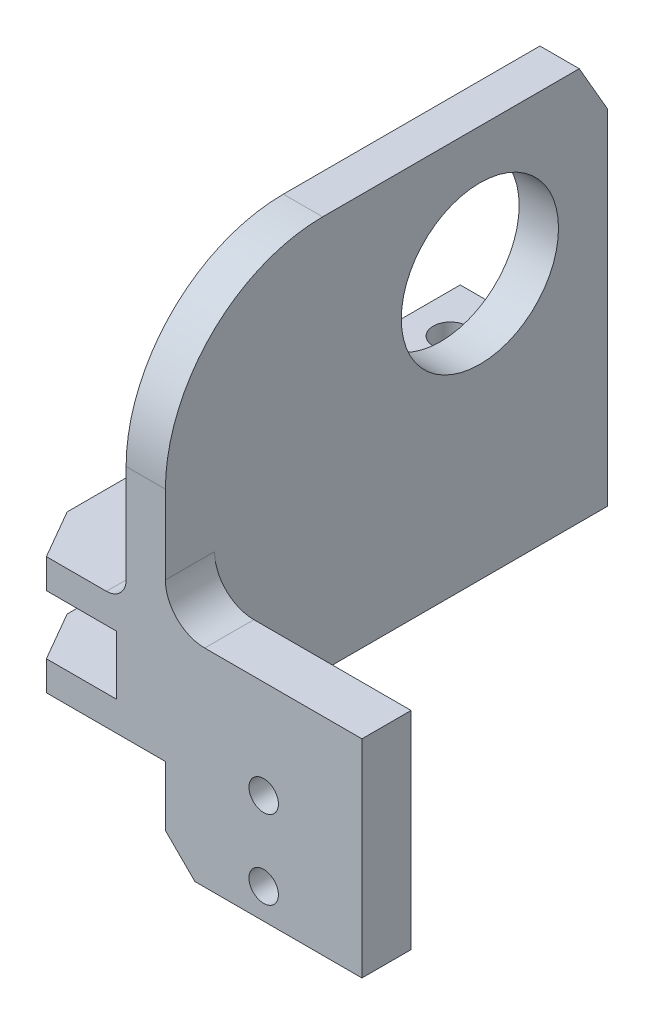
SolidWorks part; units mm, degrees
ref_plane "Piano frontale" through (0, 0, 0) normal (0, 0, 1) x (1, 0, 0)
ref_plane "Piano superiore" through (0, 0, 0) normal (0, 1, 0) x (1, 0, 0)
ref_plane "Piano destro" through (0, 0, 0) normal (1, 0, 0) x (0, 0, -1)
sketch "Schizzo1" plane through (0, 0, 0) normal (0, 0, 1) x (1, 0, 0)
  line L0 (0, 0) -> (10, 0)
  line L1 (10, 0) -> (10, -6)
  line L2 (10, -6) -> (0, -6)
  line L3 (0, 0) -> (0, 3)
  line L4 (0, 3) -> (15, 3)
  line L5 (15, 3) -> (15, -9)
  line L6 (15, -9) -> (0, -9)
  line L7 (0, -9) -> (0, -6)
  dimension "D1" = 6
  dimension "D2" = 3
  dimension "D3" = 3
  dimension "D4" = 10
  dimension "D5" = 15
extrude "Estrusione-Estrusione1" add sketch "Schizzo1" along normal blind 45
sketch "Schizzo2" plane through (15, 0, 0) normal (1, 0, 0) x (0, 0, -1)
  line L0 (-45, 3) -> (0, 3) construction
  line L1 (-45, 3) -> (-40, 3)
  line L2 (-45, 3) -> (-45, -18.078)
  line L3 (-45, -18.078) -> (-40, -18.078)
  line L4 (-40, 3) -> (-40, -18.078)
  line L5 (-45, -9) -> (-45, 3) construction
  dimension "D1" = 5
extrude "Estrusione-Estrusione2" add sketch "Schizzo2" along normal blind 20
sketch "Schizzo3" plane through (0, 3, 0) normal (0, 1, 0) x (1, 0, 0)
  line L0 (15, -20) -> (0, -20) construction
  line L1 (15, -40) -> (15, 0) construction
  line L2 (0, -45) -> (0, 0) construction
  line L3 (15, 0) -> (15, -45)
  line L4 (15, 0) -> (11, 0)
  line L5 (35, -45) -> (0, -45) construction
  line L6 (15, -45) -> (11, -45)
  line L7 (11, -45) -> (11, 0)
  dimension "D1" = 4
extrude "Estrusione-Estrusione3" add sketch "Schizzo3" along normal blind 28
sketch "Schizzo4" plane through (11, 0, 0) normal (-1, 0, 0) x (0, 0, 1)
  line L0 (0, 3) -> (45, 3) construction
  line L4 (0, 31) -> (0, 3) construction
  circle A0 centre (13, 18) radius 8
  point P4 (0, 21.3871)
  point P5 (0.3807, 20.9027)
  dimension "D1" = 16
  dimension "D2" = 15
  dimension "D3" = 13
extrude "Taglio-Estrusione1" cut sketch "Schizzo4" against normal blind 28
chamfer "Smusso1" distance 5 angle 30 1 edges at (13, 31, 0) first distance on face at (7.75, 5.2, 0)
sketch "Schizzo5" plane through (0, 3, 0) normal (0, 1, 0) x (1, 0, 0)
  line L2 (5.5, -15) -> (5.5, 0) construction
  line L3 (11, 0) -> (0, 0) construction
  circle A0 centre (4, -5) radius 1.75
  circle A1 centre (4, -25) radius 1.75
  dimension "D1" = 3.5
  dimension "D3" = 1.5
extrude "Taglio-Estrusione2" cut sketch "Schizzo5" against normal blind 28
fillet "Raccordo1" radius 2 1 edges type face fillet first side face at (11, 18, 21) second side face at (4, 3, 23.25)
chamfer "Smusso3" distance 5 angle 30 1 edges at (0, 1.5, 45) first distance on face at (0, 1.5, 22.5)
chamfer "Smusso4" distance 5 angle 30 1 edges at (0, -7.5, 45) first distance on face at (0, -7.5, 22.5)
sketch "Schizzo7" plane through (0, 0, 45) normal (0, 0, 1) x (1, 0, 0)
  line L0 (25, 8.4837) -> (25, -16.9943) construction
  line L1 (35, 3) -> (35, -18.078) construction
  line L2 (35, 3) -> (15, 3) construction
  circle A0 centre (25, -7) radius 1.5
  circle A1 centre (25, -15) radius 1.5
  dimension "D4" = 3
  dimension "D1" = 10
  dimension "D2" = 8
  dimension "D3" = 10
extrude "Taglio-Estrusione3" cut sketch "Schizzo7" against normal blind 28
chamfer "Smusso5" distance 3 angle 45 1 edges at (15, -18.078, 42.5)
fillet "Raccordo3" radius 4 1 edges type face fillet first side face at (15, 10, 13) second side face at (30, 3, 43.125)
fillet "Raccordo4" radius 16 1 edges at (13, 31, 45) type face fillet first side face at (13, 31, 23.9434) second side face at (26.5, -15, 45)
